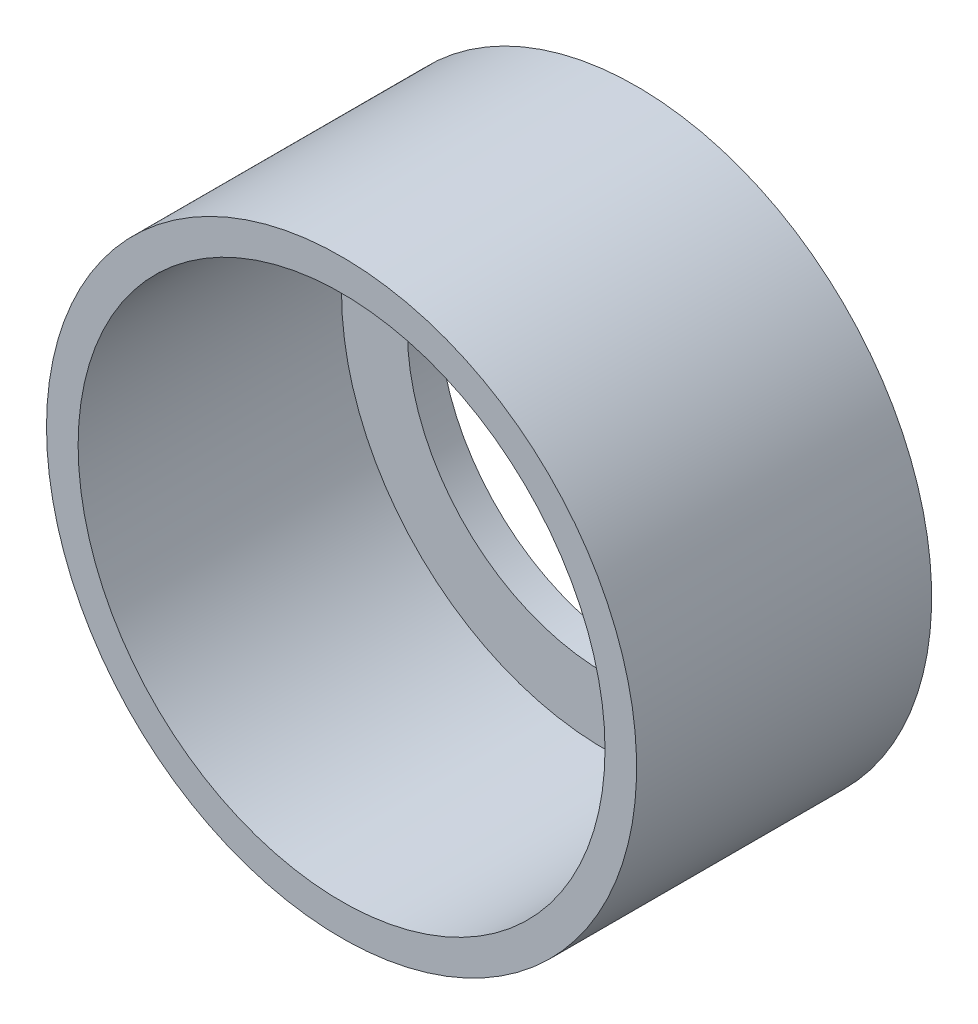
SolidWorks part; units mm, degrees
ref_plane "Front Plane" through (0, 0, 0) normal (0, 0, 1) x (1, 0, 0)
ref_plane "Top Plane" through (0, 0, 0) normal (0, 1, 0) x (1, 0, 0)
ref_plane "Right Plane" through (0, 0, 0) normal (1, 0, 0) x (0, 0, -1)
sketch "Sketch1" plane through (0, 0, 0) normal (0, 1, 0) x (1, 0, 0)
  line L0 (0, 10.179) -> (0, 0) construction
  line L1 (12.7, 5.4256) -> (14.224, 5.4256)
  line L2 (14.224, 5.4256) -> (14.224, 19.6496)
  line L3 (14.224, 19.6496) -> (9.525, 19.6496)
  line L4 (9.525, 19.6496) -> (9.525, 18.1256)
  line L5 (9.525, 18.1256) -> (12.7, 18.1256)
  line L6 (12.7, 18.1256) -> (12.7, 5.4256)
  dimension "D1" = 1.524
  dimension "D2" = 12.7
  dimension "D3" = 9.525
  dimension "D4" = 1.524
  dimension "D5" = 12.7
revolve "Revolve1" add sketch "Sketch1" angle 360 about L0
